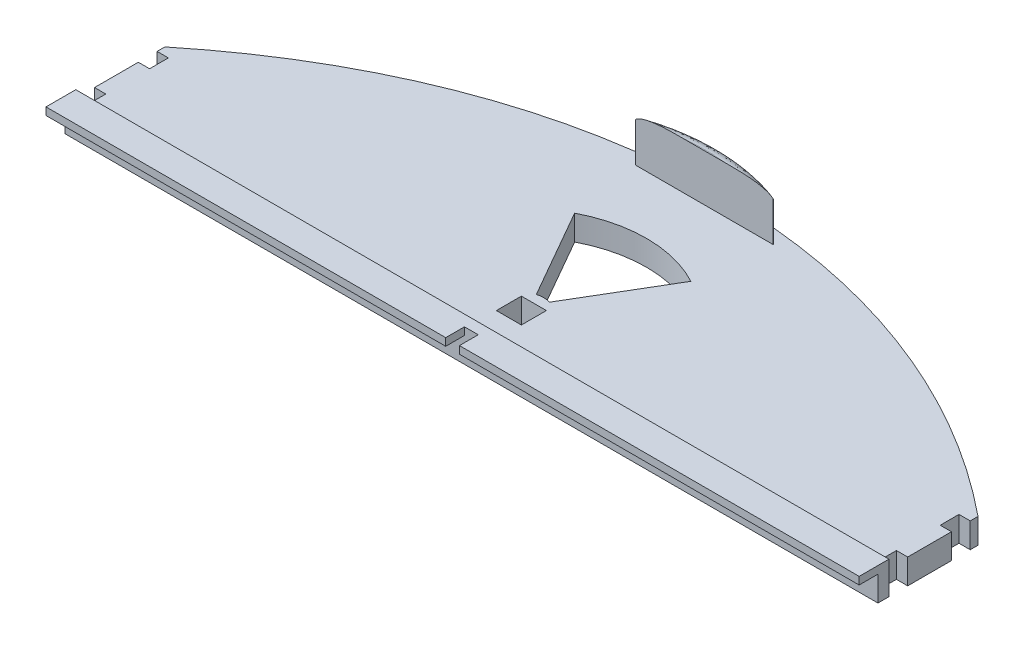
SolidWorks part; units mm, degrees
ref_plane "Front Plane" through (0, 0, 0) normal (0, 0, 1) x (1, 0, 0)
ref_plane "Top Plane" through (0, 0, 0) normal (0, 1, 0) x (1, 0, 0)
ref_plane "Right Plane" through (0, 0, 0) normal (1, 0, 0) x (0, 0, -1)
sketch "Sketch2" plane through (0, 0, 0) normal (0, 1, 0) x (1, 0, 0)
  line L0 (0, 0) -> (130, 0)
  line L1 (130, 0) -> (130, 16)
  line L2 (0, 0) -> (0, 16)
  conic Q0 (0, 16) -> (130, 16) control (65, 68.961) rho 0.453164
  point P6 (65, 0)
  dimension "D1" = 130
  dimension "D2" = 16
  dimension "D3" = 40
extrude "Boss-Extrude1" add sketch "Sketch2" along normal blind 4
ref_plane "Plane1" through (0, 4, 0) normal (0, 1, 0) x (1, 0, 0)
sketch "Sketch3" plane through (0, 4, 0) normal (0, 1, 0) x (1, 0, 0)
  line L0 (0, 1.76) -> (130, 1.76)
  line L1 (0, 16) -> (0, 0) construction
  line L2 (130, 0) -> (130, 16) construction
  line L3 (130, 1.76) -> (130, -3)
  line L4 (130, -3) -> (66.1, -3)
  line L5 (0, -3) -> (0, 1.76)
  line L6 (63.9, -3) -> (63.9, 0)
  line L7 (0, 0) -> (130, 0) construction
  line L8 (63.9, 0) -> (66.1, 0)
  line L9 (66.1, 0) -> (66.1, -3)
  line L10 (63.9, -3) -> (0, -3)
  line L11 (0, 0) -> (130, 0) construction
  point P14 (65, 0)
  point P19 (65, 0)
  dimension "D1" = 1.76
  dimension "D2" = 4.76
  dimension "D3" = 2.2
extrude "Boss-Extrude2" add sketch "Sketch3" along normal blind 1.2
sketch "Sketch4" plane through (0, 4, 0) normal (0, 1, 0) x (1, 0, 0)
  line L0 (54, 37.26) -> (76, 37.26)
  line L1 (76, 37.26) -> (76, 37.46)
  line L2 (54, 37.26) -> (54, 37.46)
  line L3 (130, 1.76) -> (0, 1.76) construction
  conic Q0 (54, 37.46) -> (76, 37.46) control (65, 41.8734) rho 0.453164
  point P9 (65, 1.76)
  dimension "D2" = 0.2
  dimension "D3" = 22
  dimension "D4" = 35.5
  dimension "D5" = 2.2
extrude "Boss-Extrude3" add sketch "Sketch4" along normal blind 7.5
fillet "Fillet1" radius 1 2 edges at (76, 7.75, -37.46) (54, 7.75, -37.46)
fillet "Fillet2" radius 2 1 edges
ref_plane "Plane2" through (0, 0, 0) normal (-1, 0, 0) x (0, 0, 1)
ref_plane "Plane3" through (130, 0, 0) normal (1, 0, 0) x (0, 0, -1)
sketch "Sketch5" plane through (130, 0, 0) normal (1, 0, 0) x (0, 0, -1)
  line L0 (36.9605, 4) -> (-36.9605, 4) construction
  line L1 (1.76, 4) -> (4.76, 4)
  line L2 (1.76, 4) -> (1.76, 0)
  line L3 (1.76, 0) -> (4.76, 0)
  line L4 (4.76, 4) -> (4.76, 0)
  line L5 (0, 0) -> (16, 0) construction
  line L6 (1.76, 5.2) -> (1.76, 4) construction
  line L8 (11.76, 4) -> (14.76, 4)
  line L9 (11.76, 4) -> (11.76, 0)
  line L10 (11.76, 0) -> (14.76, 0)
  line L11 (14.76, 4) -> (14.76, 0)
  dimension "D1" = 0
  dimension "D2" = 3
  dimension "D3" = 3
  dimension "D4" = 7
extrude "Cut-Extrude1" cut sketch "Sketch5" against normal blind 1.8
sketch "Sketch6" plane through (0, 0, 0) normal (-1, 0, 0) x (0, 0, 1)
  line L0 (-16, 4) -> (-1.76, 4) construction
  line L1 (-1.76, 4) -> (-4.76, 4)
  line L2 (-1.76, 4) -> (-1.76, 0)
  line L3 (-1.76, 0) -> (-4.76, 0)
  line L4 (-4.76, 4) -> (-4.76, 0)
  line L5 (-16, 0) -> (0, 0) construction
  line L7 (-11.76, 4) -> (-14.76, 4)
  line L8 (-11.76, 4) -> (-11.76, 0)
  line L9 (-11.76, 0) -> (-14.76, 0)
  line L10 (-14.76, 4) -> (-14.76, 0)
  dimension "D1" = 0
  dimension "D2" = 3
  dimension "D3" = 3
  dimension "D4" = 7
extrude "Cut-Extrude2" cut sketch "Sketch6" against normal blind 1.8
ref_plane "Plane4" through (0, 0, 0) normal (0, -1, 0) x (-1, 0, 0)
sketch "Sketch7" plane through (0, 0, 0) normal (0, -1, 0) x (1, 0, 0)
  line L0 (65, -8) -> (65, -28) construction
  line L1 (66.0855, -11.4065) -> (74.5, -25.5997)
  line L2 (63.967, -11.4228) -> (55.7718, -25.7438)
  line L3 (0, 0) -> (130, 0) construction
  line L5 (67, -6) -> (63, -6)
  line L6 (67, -6) -> (67, -10)
  line L7 (67, -10) -> (63, -10)
  line L8 (63, -6) -> (63, -10)
  arc A0 (55.7718, -25.7438) -> (74.5, -25.5997) centre (65, -8) ccw
  arc A1 (63.967, -11.4228) -> (66.0855, -11.4065) centre (65, -8) ccw
  circle A2 centre (65, -8) radius 1.25 construction
  point P10 (65, 0)
  point P14 (63, -8)
  point P15 (65, -10)
  dimension "D1" = 40
  dimension "D4" = 2.5
  dimension "D2" = 9.5
  dimension "D3" = 9.5
  dimension "D5" = 3.4228
  dimension "D6" = 16.5
  dimension "D7" = 8
  dimension "D8" = 4
  dimension "D9" = 4
extrude "Cut-Extrude4" cut sketch "Sketch7" against normal up to next
